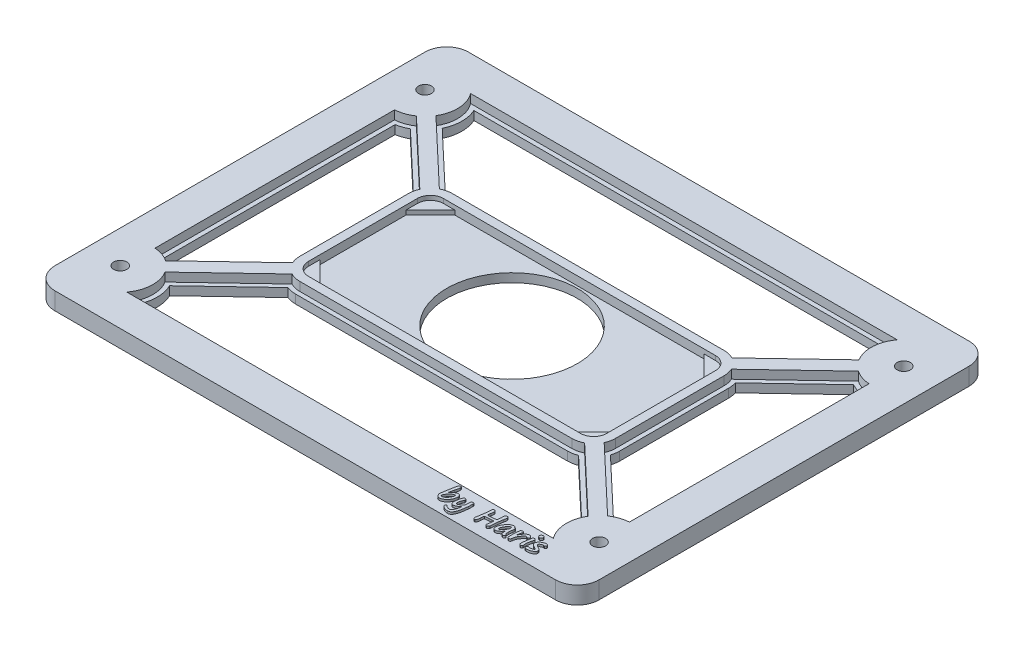
SolidWorks part; units mm, degrees
ref_plane "Front Plane" through (0, 0, 0) normal (0, 0, 1) x (1, 0, 0)
ref_plane "Top Plane" through (0, 0, 0) normal (0, 1, 0) x (1, 0, 0)
ref_plane "Right Plane" through (0, 0, 0) normal (1, 0, 0) x (0, 0, -1)
ref_plane "TerraBee_Top" through (0, 30, 0) normal (0, 1, 0) x (1, 0, 0)
sketch "Sketch1" plane through (0, 30, 0) normal (0, 1, 0) x (1, 0, 0)
  line L1 (-55, 35) -> (55, 35) construction
  line L2 (-55, 35) -> (-55, -35) construction
  line L3 (-55, -35) -> (55, -35) construction
  line L4 (55, 35) -> (55, -35) construction
  line L5 (-55, 35) -> (55, -35) construction
  line L6 (-55, -35) -> (55, 35) construction
  line L15 (-57.5, 47.5) -> (57.5, 47.5)
  line L16 (-62.5, 42.5) -> (-62.5, -42.5)
  line L17 (-57.5, -47.5) -> (57.5, -47.5)
  line L18 (62.5, 42.5) -> (62.5, -42.5)
  line L19 (-62.5, 47.5) -> (62.5, -47.5) construction
  line L20 (-62.5, -47.5) -> (62.5, 47.5) construction
  circle A0 centre (-55, -35) radius 1.5
  circle A1 centre (55, -35) radius 1.5
  circle A2 centre (55, 35) radius 1.5
  circle A3 centre (-55, 35) radius 1.5
  arc A4 (-62.5, -42.5) -> (-57.5, -47.5) centre (-57.5, -42.5) ccw
  arc A5 (57.5, -47.5) -> (62.5, -42.5) centre (57.5, -42.5) ccw
  arc A6 (57.5, 47.5) -> (62.5, 42.5) centre (57.5, 42.5) cw
  arc A7 (-57.5, 47.5) -> (-62.5, 42.5) centre (-57.5, 42.5) ccw
  point P0 (0, 0)
  point P10 (0, 0)
  dimension "D3" = 3
  dimension "D6" = 5
  dimension "D1" = 70
  dimension "D2" = 110
  dimension "D4" = 95
  dimension "D5" = 125
extrude "Boss-Extrude1" add sketch "Sketch1" along normal blind 4
sketch "Arduino_Cutout" plane through (0, 34, 0) normal (0, 1, 0) x (1, 0, 0)
  line L17 (60.1624, 0) -> (0, 0) construction
  line L18 (0, -40.5715) -> (0, 0) construction
  line L19 (-31.25, 17.5) -> (31.25, 17.5)
  line L20 (-31.25, 15.5) -> (31.25, 15.5)
  line L21 (-34.25, 12.5) -> (-34.25, -12.5)
  line L22 (-31.25, -15.5) -> (31.25, -15.5)
  line L27 (-54.5, -39.5) -> (54.5, -39.5)
  line L28 (54.5, -39.5) -> (54.5, 39.5)
  line L29 (54.5, 39.5) -> (-54.5, 39.5)
  line L30 (-54.5, 39.5) -> (-54.5, -39.5)
  line L31 (-49, -39.5) -> (49, -39.5)
  line L32 (54.5, -27.5167) -> (54.5, 27.5167)
  line L33 (49, 39.5) -> (-49, 39.5)
  line L34 (-54.5, 27.5167) -> (-54.5, -27.5167)
  line L49 (34.25, 12.5) -> (34.25, -12.5)
  line L50 (-34.25, 15.5) -> (34.25, -15.5) construction
  line L51 (-34.25, -15.5) -> (34.25, 15.5) construction
  line L52 (36.25, 12.5) -> (36.25, -12.5)
  line L53 (-31.25, -17.5) -> (31.25, -17.5)
  line L54 (-36.25, 12.5) -> (-36.25, -12.5)
  line L55 (-55, 35) -> (-31.25, 12.5) construction
  arc A40 (-34.25, -12.5) -> (-31.25, -15.5) centre (-31.25, -12.5) ccw
  arc A41 (-31.25, 15.5) -> (-34.25, 12.5) centre (-31.25, 12.5) ccw
  arc A42 (31.25, 15.5) -> (34.25, 12.5) centre (31.25, 12.5) cw
  arc A43 (31.25, -15.5) -> (34.25, -12.5) centre (31.25, -12.5) ccw
  arc A44 (-54.5, 27.5167) -> (-49.5554, 29.8419) centre (-55, 35) ccw
  arc A45 (49, 39.5) -> (54.5, 27.5167) centre (55, 35) ccw
  arc A46 (54.5, -27.5167) -> (49, -39.5) centre (55, -35) ccw
  arc A47 (-49, -39.5) -> (-54.5, -27.5167) centre (-55, -35) ccw
  arc A48 (31.25, 17.5) -> (36.25, 12.5) centre (31.25, 12.5) cw
  arc A49 (31.25, -17.5) -> (36.25, -12.5) centre (31.25, -12.5) ccw
  arc A50 (-36.25, -12.5) -> (-31.25, -17.5) centre (-31.25, -12.5) ccw
  arc A51 (-31.25, 17.5) -> (-32.7655, 17.2648) centre (-31.25, 12.5) ccw
  arc A52 (-49.5554, 29.8419) -> (-49, 39.5) centre (-55, 35) ccw
  arc A53 (-36.0897, 13.7559) -> (-36.25, 12.5) centre (-31.25, 12.5) ccw
  arc A54 (-31.25, 17.5) -> (-36.25, 12.5) centre (-31.25, 12.5) ccw construction
  arc A55 (-32.7655, 17.2648) -> (-36.0897, 13.7559) centre (-31.25, 12.5) ccw
  dimension "D2" = 68.5
  dimension "D3" = 15
  dimension "D5" = 3
  dimension "D1" = 31
  dimension "D4" = 8
  dimension "D6" = 2
extrude "Cut-Extrude1" cut sketch "Arduino_Cutout" against normal blind 2 contours A47 L31 A46 L32 A45 L33 A44 L34 | L21 A40 L22 A43 L49 A42 L20 A41 region at (-46.9602, 34, 31.31)
sketch "Sketch6" plane through (0, 32, 0) normal (0, 1, 0) x (1, 0, 0)
  line L1 (28.6399, -15.5) -> (34.25, -9.8899)
  line L5 (-31.25, -15.5) -> (31.25, -15.5) construction
  line L9 (34.25, 12.5) -> (34.25, -12.5) construction
  line L13 (34.25, -9.8899) -> (34.25, -12.5)
  line L17 (28.6399, 15.5) -> (34.25, 9.8899)
  line L18 (34.25, 9.8899) -> (34.25, 12.5069)
  line L19 (31.25, 15.5) -> (28.6399, 15.5)
  line L20 (-34.25, 9.8899) -> (-34.25, 12.5069)
  line L21 (31.25, -15.5) -> (28.6399, -15.5)
  line L22 (34.25, 12.5) -> (34.25, -12.5) construction
  line L23 (0, 0) -> (29.8553, 0) construction
  line L24 (0, 0) -> (0, 20.6855) construction
  line L25 (-31.25, 15.5) -> (-28.6399, 15.5)
  line L26 (-28.6399, 15.5) -> (-34.25, 9.8899)
  line L27 (-28.6399, -15.5) -> (-34.25, -9.8899)
  line L28 (-34.25, -9.8899) -> (-34.25, -12.5)
  line L29 (-31.25, -15.5) -> (-28.6399, -15.5)
  arc A10 (34.25, -12.5) -> (31.25, -15.5) centre (31.25, -12.5) cw
  arc A11 (34.25, 12.5069) -> (31.25, 15.5) centre (31.25, 12.5) ccw
  arc A12 (-34.25, 12.5069) -> (-31.25, 15.5) centre (-31.25, 12.5) cw
  arc A13 (-34.25, -12.5) -> (-31.25, -15.5) centre (-31.25, -12.5) ccw
  point P29 (0, 0)
extrude "Boss-Extrude5" add sketch "Sketch6" along normal blind 1
sketch "Sketch5" plane through (0, 30, 0) normal (0, -1, 0) x (1, 0, 0)
  circle A0 centre (0, 0) radius 40
  circle A1 centre (0, 0) radius 35
  dimension "D1" = 80
  dimension "D2" = 5
extrude "TerraBee" [suppressed] add sketch "Sketch5" along normal blind 10
sketch "Sketch11" plane through (0, 32, 0) normal (0, 1, 0) x (1, 0, 0)
  line L0 (-31.25, 12.5) -> (-55, 35) construction
  line L1 (-50.7703, 28.8065) -> (-35.7836, 14.6086)
  line L2 (-48.5871, 31.111) -> (-33.6004, 16.9131)
  line L3 (-50.7703, 28.8065) -> (-48.5871, 31.111)
  line L4 (-33.6004, 16.9131) -> (-35.7836, 14.6086)
  line L5 (0, -2.475) -> (0, 2.475) construction
  line L6 (48.5871, 31.111) -> (33.6004, 16.9131)
  line L7 (50.7703, 28.8065) -> (48.5871, 31.111)
  line L8 (50.7703, 28.8065) -> (35.7836, 14.6086)
  line L9 (33.6004, 16.9131) -> (35.7836, 14.6086)
  line L10 (-2.475, 0) -> (2.475, 0) construction
  line L11 (-48.5871, -31.111) -> (-33.6004, -16.9131)
  line L12 (-50.7703, -28.8065) -> (-48.5871, -31.111)
  line L13 (-50.7703, -28.8065) -> (-35.7836, -14.6086)
  line L14 (-33.6004, -16.9131) -> (-35.7836, -14.6086)
  line L15 (50.7703, -28.8065) -> (48.5871, -31.111)
  line L16 (50.7703, -28.8065) -> (35.7836, -14.6086)
  line L17 (33.6004, -16.9131) -> (35.7836, -14.6086)
  line L18 (48.5871, -31.111) -> (33.6004, -16.9131)
  arc A0 (-54.5, 27.5167) -> (-49, 39.5) centre (-55, 35) ccw construction
  arc A1 (-31.25, 17.5) -> (-36.25, 12.5) centre (-31.25, 12.5) ccw construction
extrude "Boss-Extrude6" add sketch "Sketch11" along normal blind 2
sketch "Sketch8" plane through (0, 32, 0) normal (0, 1, 0) x (1, 0, 0)
  line L14 (47.3428, -31.3098) -> (33.4006, -18.1013)
  line L15 (31.25, -18.5) -> (-31.25, -18.5)
  line L16 (-33.4006, -18.1013) -> (-47.3428, -31.3098)
  line L17 (-47.254, -38.5) -> (47.254, -38.5)
  line L26 (47.3428, -31.3098) -> (33.4006, -18.1013)
  line L27 (31.25, -18.5) -> (-31.25, -18.5)
  line L28 (-33.4006, -18.1013) -> (-47.3428, -31.3098)
  line L29 (-47.254, -38.5) -> (47.254, -38.5)
  line L34 (-50.9016, -27.5533) -> (-36.9593, -14.3449)
  line L35 (-37.25, -12.5) -> (-37.25, 12.5)
  line L36 (-36.9593, 14.3449) -> (-50.9016, 27.5533)
  line L37 (-53.5, 26.6334) -> (-53.5, -26.6334)
  line L38 (-50.9016, -27.5533) -> (-36.9593, -14.3449)
  line L39 (-37.25, -12.5) -> (-37.25, 12.5)
  line L40 (-36.9593, 14.3449) -> (-50.9016, 27.5533)
  line L41 (-53.5, 26.6334) -> (-53.5, -26.6334)
  line L46 (36.9593, -14.3449) -> (50.9016, -27.5533)
  line L47 (53.5, -26.6334) -> (53.5, 26.6334)
  line L48 (50.9016, 27.5533) -> (36.9593, 14.3449)
  line L49 (37.25, 12.5) -> (37.25, -12.5)
  line L50 (36.9593, -14.3449) -> (50.9016, -27.5533)
  line L51 (53.5, -26.6334) -> (53.5, 26.6334)
  line L52 (50.9016, 27.5533) -> (36.9593, 14.3449)
  line L53 (37.25, 12.5) -> (37.25, -12.5)
  line L58 (33.4006, 18.1013) -> (47.3428, 31.3098)
  line L59 (47.254, 38.5) -> (-47.254, 38.5)
  line L60 (-47.3428, 31.3098) -> (-33.4006, 18.1013)
  line L61 (-31.25, 18.5) -> (31.25, 18.5)
  line L62 (33.4006, 18.1013) -> (47.3428, 31.3098)
  line L63 (47.254, 38.5) -> (-47.254, 38.5)
  line L64 (-47.3428, 31.3098) -> (-33.4006, 18.1013)
  line L65 (-31.25, 18.5) -> (31.25, 18.5)
  arc A22 (47.3428, -31.3098) -> (47.254, -38.5) centre (55, -35) ccw
  arc A23 (31.25, -18.5) -> (33.4006, -18.1013) centre (31.25, -12.5) ccw
  arc A24 (-33.4006, -18.1013) -> (-31.25, -18.5) centre (-31.25, -12.5) ccw
  arc A25 (-47.254, -38.5) -> (-47.3428, -31.3098) centre (-55, -35) ccw
  arc A26 (47.3428, -31.3098) -> (47.254, -38.5) centre (55, -35) ccw
  arc A27 (31.25, -18.5) -> (33.4006, -18.1013) centre (31.25, -12.5) ccw
  arc A28 (-33.4006, -18.1013) -> (-31.25, -18.5) centre (-31.25, -12.5) ccw
  arc A29 (-47.254, -38.5) -> (-47.3428, -31.3098) centre (-55, -35) ccw
  arc A34 (-50.9016, -27.5533) -> (-53.5, -26.6334) centre (-55, -35) ccw
  arc A35 (-37.25, -12.5) -> (-36.9593, -14.3449) centre (-31.25, -12.5) ccw
  arc A36 (-36.9593, 14.3449) -> (-37.25, 12.5) centre (-31.25, 12.5) ccw
  arc A37 (-53.5, 26.6334) -> (-50.9016, 27.5533) centre (-55, 35) ccw
  arc A38 (-50.9016, -27.5533) -> (-53.5, -26.6334) centre (-55, -35) ccw
  arc A39 (-37.25, -12.5) -> (-36.9593, -14.3449) centre (-31.25, -12.5) ccw
  arc A40 (-36.9593, 14.3449) -> (-37.25, 12.5) centre (-31.25, 12.5) ccw
  arc A41 (-53.5, 26.6334) -> (-50.9016, 27.5533) centre (-55, 35) ccw
  arc A46 (36.9593, -14.3449) -> (37.25, -12.5) centre (31.25, -12.5) ccw
  arc A47 (53.5, -26.6334) -> (50.9016, -27.5533) centre (55, -35) ccw
  arc A48 (50.9016, 27.5533) -> (53.5, 26.6334) centre (55, 35) ccw
  arc A49 (37.25, 12.5) -> (36.9593, 14.3449) centre (31.25, 12.5) ccw
  arc A50 (36.9593, -14.3449) -> (37.25, -12.5) centre (31.25, -12.5) ccw
  arc A51 (53.5, -26.6334) -> (50.9016, -27.5533) centre (55, -35) ccw
  arc A52 (50.9016, 27.5533) -> (53.5, 26.6334) centre (55, 35) ccw
  arc A53 (37.25, 12.5) -> (36.9593, 14.3449) centre (31.25, 12.5) ccw
  arc A58 (33.4006, 18.1013) -> (31.25, 18.5) centre (31.25, 12.5) ccw
  arc A59 (47.254, 38.5) -> (47.3428, 31.3098) centre (55, 35) ccw
  arc A60 (-47.3428, 31.3098) -> (-47.254, 38.5) centre (-55, 35) ccw
  arc A61 (-31.25, 18.5) -> (-33.4006, 18.1013) centre (-31.25, 12.5) ccw
  arc A62 (33.4006, 18.1013) -> (31.25, 18.5) centre (31.25, 12.5) ccw
  arc A63 (47.254, 38.5) -> (47.3428, 31.3098) centre (55, 35) ccw
  arc A64 (-47.3428, 31.3098) -> (-47.254, 38.5) centre (-55, 35) ccw
  arc A65 (-31.25, 18.5) -> (-33.4006, 18.1013) centre (-31.25, 12.5) ccw
  point P9 (0, -23.5)
  dimension "D1" = 1
  dimension "D2" = 1
  dimension "D3" = 1
  dimension "D4" = 1
extrude "Cut-Extrude2" cut sketch "Sketch8" against normal blind 5
sketch "Sketch9" plane through (0, 32, 0) normal (0, 1, 0) x (1, 0, 0)
  circle A0 centre (0, 0) radius 15
  dimension "D1" = 30
extrude "Cut-Extrude3" cut sketch "Sketch9" against normal blind 5
sketch "Sketch10" plane through (0, 34, 0) normal (0, 1, 0) x (1, 0, 0)
  line L0 (0, -45) -> (50.3701, -45) construction
  line L1 (-57.5, -47.5) -> (57.5, -47.5) construction
  text T0 "by Haris" font "Segoe Print" height 4
  dimension "D1" = 2.5
extrude "Boss-Extrude4" add sketch "Sketch10" along normal blind 0.5
